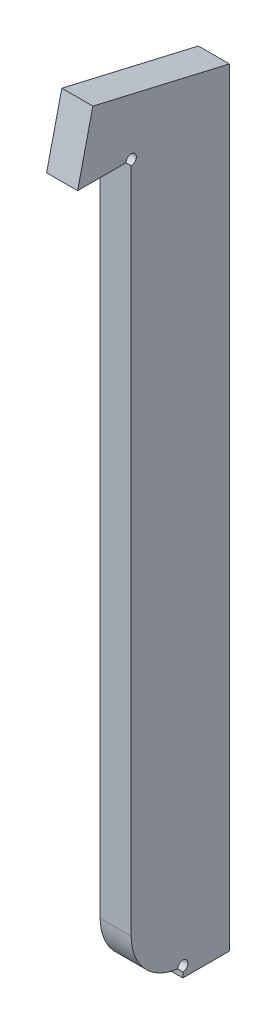
SolidWorks part; units mm, degrees
material "MDF"
ref_plane "Front Plane" through (0, 0, 0) normal (0, 0, 1) x (1, 0, 0)
ref_plane "Top Plane" through (0, 0, 0) normal (0, 1, 0) x (1, 0, 0)
ref_plane "Right Plane" through (0, 0, 0) normal (1, 0, 0) x (0, 0, -1)
sketch "Sketch1" plane through (0, 0, 0) normal (0, 0, 1) x (1, 0, 0)
  line L0 (-181.9836, -463.55) -> (-104.775, -463.55) construction
  line L1 (-228.0888, 0) -> (-209.0388, 0)
  line L2 (-228.0888, 0) -> (-228.0888, -450.85)
  line L3 (-228.0888, -450.85) -> (-209.0388, -450.85)
  line L4 (-209.0388, 0) -> (-209.0388, -450.85)
  dimension "D1" = 19.05
  dimension "D2" = 12.7
extrude "Boss-Extrude1" add sketch "Sketch1" along normal blind 66.675
fillet "Fillet4" radius 38.1 1 edges at (-218.5638, -450.85, 66.675)
sketch "Sketch4" plane through (-228.0888, 0, 0) normal (-1, 0, 0) x (0, 0, 1)
  line L1 (66.675, 0) -> (66.675, -412.75) construction
  line L3 (66.675, 0) -> (66.675, -412.75)
  line L4 (60.325, 0) -> (60.325, -412.75)
  line L5 (28.575, -450.85) -> (28.575, -444.5)
  line L6 (66.675, 0) -> (60.325, 0)
  arc A1 (28.575, -450.85) -> (66.675, -412.75) centre (28.575, -412.75) ccw construction
  arc A3 (28.575, -450.85) -> (66.675, -412.75) centre (28.575, -412.75) ccw
  arc A4 (28.575, -444.5) -> (60.325, -412.75) centre (28.575, -412.75) ccw
  dimension "D1" = 6.35
extrude "Cut-Extrude1" cut sketch "Sketch4" against normal up to next
sketch "Sketch7" plane through (-228.0888, 0, 0) normal (-1, 0, 0) x (0, 0, 1)
  line L0 (0, 0) -> (60.325, 0)
  line L1 (60.325, 0) -> (60.325, 34.8446)
  line L2 (495.3358, 135.9439) -> (380.7162, 109.3055) construction
  line L3 (60.325, 34.8446) -> (0, 20.8246)
  line L4 (0, 20.8246) -> (0, 0)
extrude "Boss-Extrude2" add sketch "Sketch7" against normal through all
sketch "Sketch8" plane through (-228.0888, 0, 0) normal (-1, 0, 0) x (0, 0, 1)
  line L0 (60.325, 34.8446) -> (83.8286, 40.3069)
  line L1 (83.8286, 40.3069) -> (93.1962, 0)
  line L2 (93.1962, 0) -> (60.325, 0)
  line L3 (60.325, 34.8446) -> (0, 20.8246) construction
  line L4 (60.325, 0) -> (60.325, 34.8446)
  dimension "D1" = 90
  dimension "D2" = 24.13
extrude "Boss-Extrude3" add sketch "Sketch8" against normal through all
chamfer "Chamfer1" [suppressed] distance 12.7 angle 45
hole_wizard "1/4 (0.25) Diameter Hole1" positions "Sketch5" profile "Sketch6" hole size "1/4" standard "ANSI Inch" end condition up to next
sketch "Sketch5" plane through (-228.0888, 0, 0) normal (-1, 0, 0) x (0, 0, 1)
  point P0 (28.575, -444.5)
  point P3 (60.325, 0)
sketch "Sketch6" plane through (-228.0888, -444.5, 28.575) normal (0, 1, 0) x (0, 0, 1)
  line L0 (0, 0) -> (0, 19.05)
  line L1 (0, 19.05) -> (3.175, 19.05)
  line L2 (3.175, 19.05) -> (3.175, 0)
  line L5 (3.175, 0) -> (0, 0)
  line L11 (0, -6.35) -> (0, 107.95) construction
  dimension "Thru Hole Dia." = 6.35
  dimension "Thru Hole Depth" = 19.05
